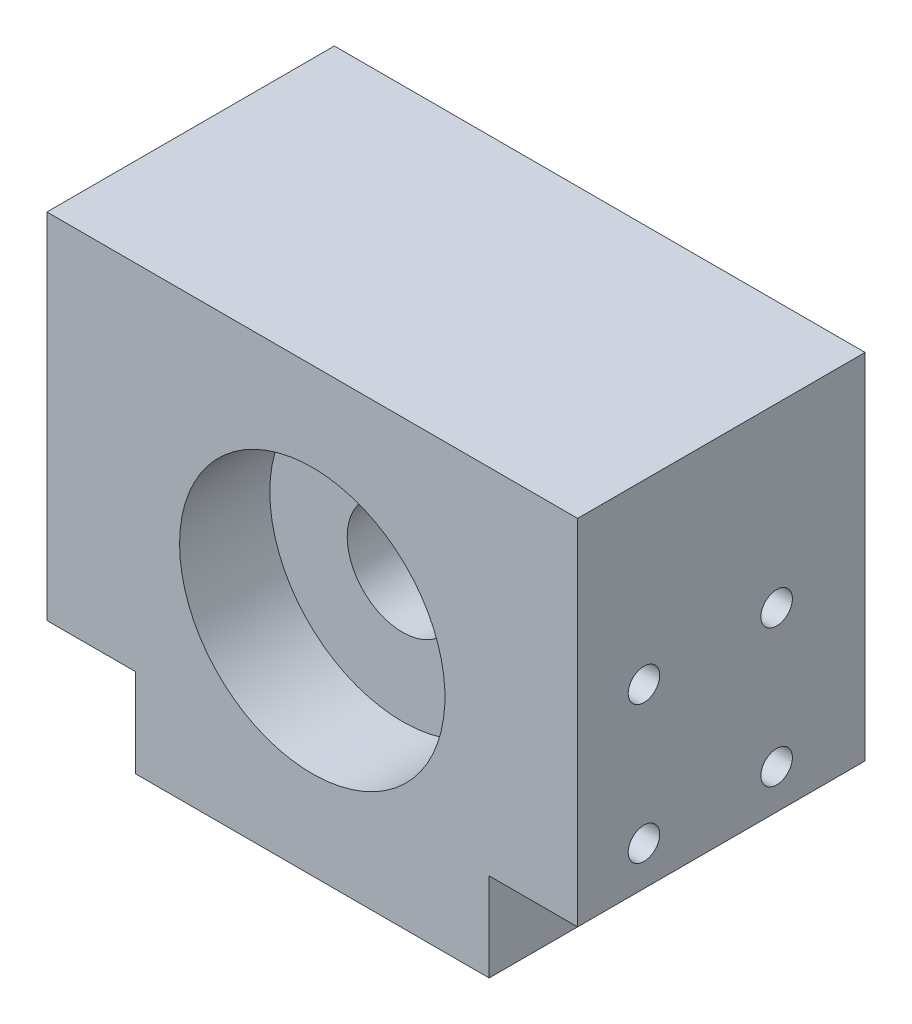
SolidWorks part; units mm, degrees
material "1060 Alloy"
ref_plane "Front" through (0, 0, 0) normal (0, 0, 1) x (1, 0, 0)
ref_plane "Top" through (0, 0, 0) normal (0, 1, 0) x (1, 0, 0)
ref_plane "Right" through (0, 0, 0) normal (1, 0, 0) x (0, 0, -1)
sketch "Sketch1" plane through (0, 0, 0) normal (0, 0, 1) x (1, 0, 0)
  line L1 (19.05, -15.875) -> (-19.05, -15.875)
  line L2 (19.05, -15.875) -> (19.05, 15.875)
  line L3 (19.05, 15.875) -> (-19.05, 15.875)
  line L4 (-19.05, -15.875) -> (-19.05, 15.875)
  line L5 (19.05, -15.875) -> (-19.05, 15.875) construction
  line L6 (19.05, 15.875) -> (-19.05, -15.875) construction
  point P0 (0, 0)
  dimension "D1" = 31.75
  dimension "D2" = 38.1
extrude "Boss-Extrude1" add sketch "Sketch1" along normal blind 20.6375
sketch "Sketch2" plane through (0, 0, 0) normal (0, 0, -1) x (-1, 0, 0)
  circle A0 centre (0, 0) radius 11.1125
  dimension "D1" = 22.225
extrude "Cut-Extrude1" cut sketch "Sketch2" against normal blind 6.985
sketch "Sketch3" plane through (0, 0, 6.985) normal (0, 0, -1) x (-1, 0, 0)
  circle A0 centre (0, 0) radius 8.255
  dimension "D1" = 16.51
extrude "Cut-Extrude2" cut sketch "Sketch3" against normal blind 2.413
sketch "Sketch4" plane through (0, 0, 9.398) normal (0, 0, -1) x (-1, 0, 0)
  circle A0 centre (0, 0) radius 3.9688
  dimension "D1" = 7.9375
extrude "Cut-Extrude3" cut sketch "Sketch4" against normal through all
sketch "Sketch6" plane through (0, 0, 9.398) normal (0, 0, -1) x (-1, 0, 0)
  circle A0 centre (0, 0) radius 9.525
  dimension "D1" = 19.05
extrude "Cut-Extrude4" cut sketch "Sketch6" against normal through all from offset 4.7625 offset against normal yes
hole_wizard "#4-40 Tapped Hole2" positions "Sketch7" profile "Sketch8" tap size "#4-40" standard "ANSI Inch"
sketch "Sketch7" plane through (-19.05, -28.277, 98.8948) normal (-1, 0, 0) x (0, 0, 1)
  point P0 (-92.5448, 31.452)
  point P1 (-83.0198, 31.452)
  point P2 (-83.0198, 21.927)
  point P3 (-92.5448, 21.927)
sketch "Sketch8" plane through (-19.05, 3.175, 6.35) normal (0, 1, 0) x (0, 0, 1)
  line L0 (0, 0) -> (0, 8.2992)
  line L1 (0, 8.2992) -> (1.1303, 7.62)
  line L2 (1.1303, 7.62) -> (1.1303, 0)
  line L5 (1.1303, 0) -> (0, 0)
  line L10 (0, 8.2992) -> (-1.1303, 7.62) construction
  line L11 (0, -6.35) -> (0, 107.95) construction
  dimension "Tap Drill Dia." = 2.2606
  dimension "Tap Drill Depth" = 7.62
  dimension "Drill Angle" = 118
cosmetic thread "Hole Thread5" parameters "D1"=5.588, "D2"=2.8448
cosmetic thread "Hole Thread6" parameters "D1"=5.588, "D2"=2.8448
cosmetic thread "Hole Thread7" parameters "D1"=5.588, "D2"=2.8448
cosmetic thread "Hole Thread8" parameters "D1"=5.588, "D2"=2.8448
hole_wizard "#4-40 Tapped Hole1" positions "Sketch11" profile "Sketch12" tap size "#4-40" standard "ANSI Inch"
sketch "Sketch11" plane through (19.05, -28.277, 98.8948) normal (1, 0, 0) x (0, 0, -1)
  point P0 (92.5448, 31.452)
  point P1 (83.0198, 31.452)
  point P2 (83.0198, 21.5728)
  point P3 (92.5448, 21.5728)
cosmetic thread "Hole Thread1" parameters "D1"=5.588, "D2"=2.8448
cosmetic thread "Hole Thread2" parameters "D1"=5.588, "D2"=2.8448
cosmetic thread "Hole Thread3" parameters "D1"=5.588, "D2"=2.8448
cosmetic thread "Hole Thread4" parameters "D1"=5.588, "D2"=2.8448
sketch "Sketch12" plane through (19.05, 3.175, 6.35) normal (0, 1, 0) x (0, 0, -1)
  line L0 (0, 0) -> (0, 8.2992)
  line L1 (0, 8.2992) -> (1.1303, 7.62)
  line L2 (1.1303, 7.62) -> (1.1303, 0)
  line L5 (1.1303, 0) -> (0, 0)
  line L10 (0, 8.2992) -> (-1.1303, 7.62) construction
  line L11 (0, -6.35) -> (0, 107.95) construction
  dimension "Tap Drill Dia." = 2.2606
  dimension "Tap Drill Depth" = 7.62
  dimension "Drill Angle" = 118
sketch "Sketch13" plane through (0, 0, 20.6375) normal (0, 0, 1) x (1, 0, 0)
  line L0 (0, 0) -> (0, 49.175) construction
  line L1 (-19.05, -9.525) -> (-12.7, -9.525)
  line L2 (-19.05, -9.525) -> (-19.05, -15.875)
  line L3 (-19.05, -15.875) -> (-12.7, -15.875)
  line L4 (-12.7, -9.525) -> (-12.7, -15.875)
  line L5 (19.05, -15.875) -> (12.7, -15.875)
  line L6 (19.05, -9.525) -> (19.05, -15.875)
  line L7 (19.05, -9.525) -> (12.7, -9.525)
  line L8 (12.7, -9.525) -> (12.7, -15.875)
  point P12 (0, 0)
  point P13 (0, 0)
  point P14 (0, 0)
  point P15 (0, 0)
  point P16 (0, 0)
  point P18 (0, 0)
  dimension "D1" = 25.4
  dimension "D2" = 6.35
extrude "Cut-Extrude5" cut sketch "Sketch13" against normal up to surface (20.6375 mm away) up to face at (-11.1125, 0, 0)
